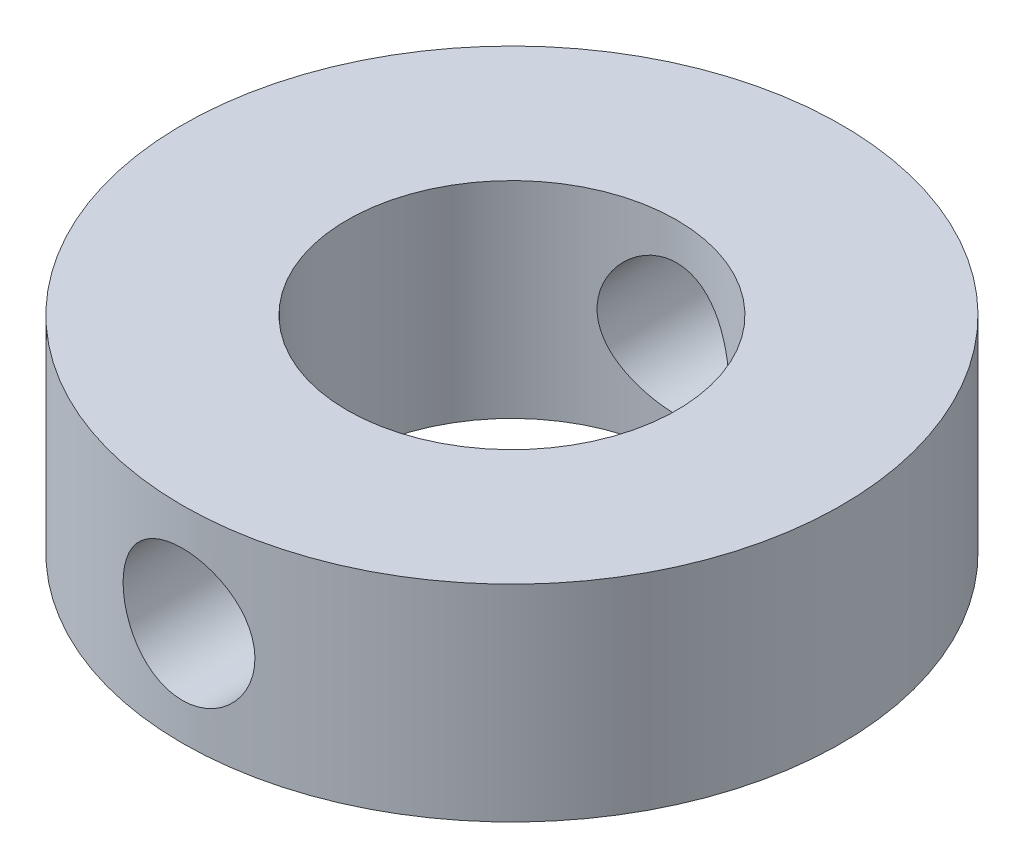
SolidWorks part; units mm, degrees
ref_plane "Plan de face" through (0, 0, 0) normal (0, 0, 1) x (1, 0, 0)
ref_plane "Plan de dessus" through (0, 0, 0) normal (0, 1, 0) x (1, 0, 0)
ref_plane "Plan de droite" through (0, 0, 0) normal (1, 0, 0) x (0, 0, -1)
sketch "Esquisse1" plane through (0, 0, 0) normal (0, 1, 0) x (1, 0, 0)
  circle A0 centre (0, 0) radius 8
  circle A1 centre (0, 0) radius 4
  dimension "D1" = 16
extrude "Boss.-Extru.1" add sketch "Esquisse1" along normal blind 2.5
extrude "Boss.-Extru.2" add sketch "Esquisse1<2>" against normal blind 2.5
sketch "Esquisse1<2>" plane through (0, 0, 0) normal (0, 1, 0) x (1, 0, 0) same geometry as "Esquisse1"
sketch "Esquisse2" plane through (0, 0, 0) normal (0, 0, 1) x (1, 0, 0)
  circle A0 centre (0, 0) radius 1.6
extrude "Enlèv. mat.-Extru.1" cut sketch "Esquisse2" against normal blind 50 and the other way blind 50
